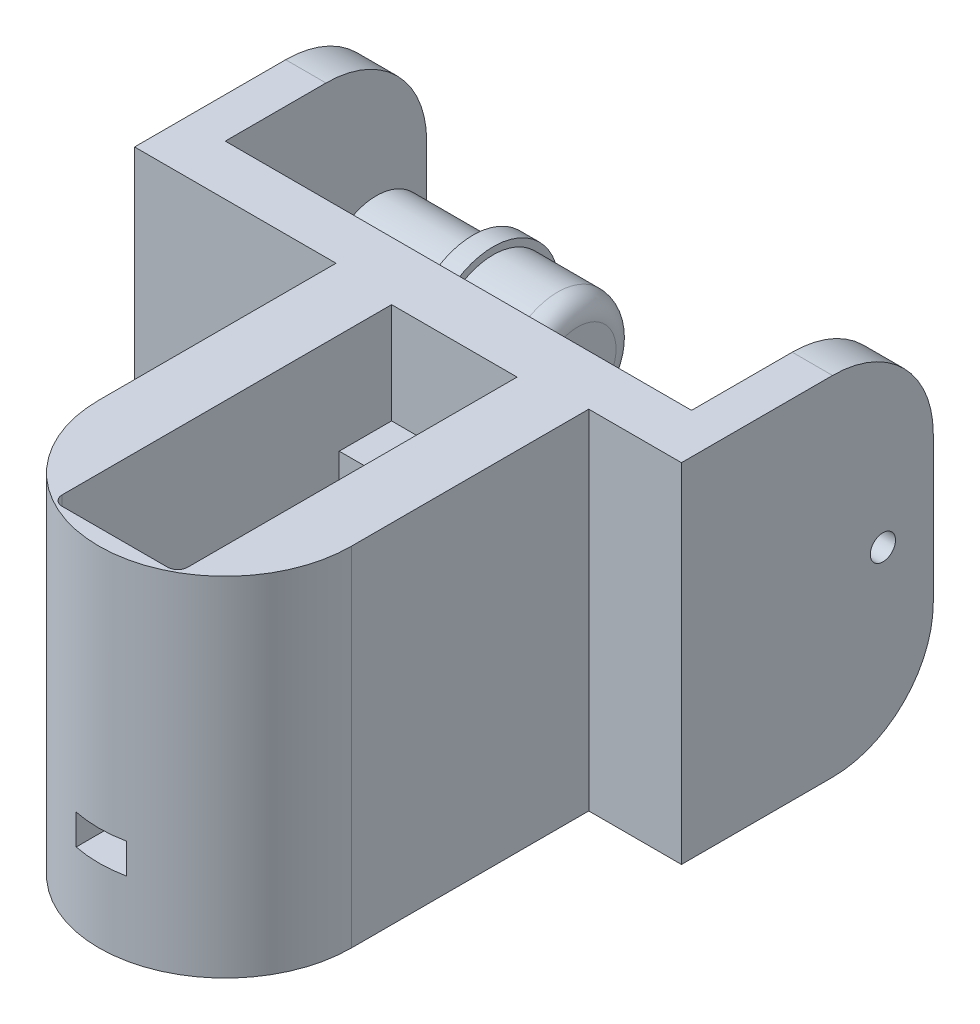
SolidWorks part; units mm, degrees
ref_plane "Front Plane" through (0, 0, 0) normal (0, 0, 1) x (1, 0, 0)
ref_plane "Top Plane" through (0, 0, 0) normal (0, 1, 0) x (1, 0, 0)
ref_plane "Right Plane" through (0, 0, 0) normal (1, 0, 0) x (0, 0, -1)
sketch "Sketch4" plane through (0, 0, 0) normal (0, 0, 1) x (1, 0, 0)
  line L1 (-6.23, -9.975) -> (6.23, -9.975)
  line L2 (-6.23, -9.975) -> (-6.23, 7.275)
  line L3 (-6.23, 7.275) -> (6.23, 7.275)
  line L4 (6.23, -9.975) -> (6.23, 7.275)
  point P4 (0, 7.275)
  dimension "D1" = 12.46
  dimension "D2" = 17.25
  dimension "D3" = 9.975
extrude "Boss-Extrude3" add sketch "Sketch4" along normal blind 6
sketch "Sketch8" plane through (0, -9.975, 0) normal (0, -1, 0) x (-1, 0, 0)
  circle A0 centre (0, -23.55) radius 12.5468
  circle A1 centre (0, -23.55) radius 11.15
  dimension "D1" = 22.3
  dimension "D2" = 23.55
extrude "Boss-Extrude6" add sketch "Sketch8" along normal blind 7.3 and the other way up to surface (17.25 mm away) other way up to face at (0, 7.275, 3)
sketch "Sketch5" plane through (0, 7.275, 0) normal (0, 1, 0) x (1, 0, 0)
  line L8 (12.5468, -23.55) -> (12.5468, 0)
  line L9 (12.5468, 0) -> (6.23, 0)
  line L10 (-12.5468, -23.55) -> (-12.5468, 0)
  line L11 (-12.5468, 0) -> (-6.23, 0)
  line L12 (-6.23, 0) -> (-6.23, -29.7)
  line L14 (6.23, -29.7) -> (6.23, 0)
  line L15 (-6.23, -29.7) -> (6.23, -29.7)
  line L16 (6.23, -6) -> (-6.23, -6) construction
  circle A0 centre (0, -23.55) radius 12.5468 construction
  arc A1 (-12.5468, -23.55) -> (12.5468, -23.55) centre (0, -23.55) ccw
  dimension "D1" = 23.7
  dimension "D2" = 23.55
extrude "Boss-Extrude4" add sketch "Sketch5" against normal up to surface (17.25 mm away) up to face at (0, -9.975, 3)
sketch "Sketch6" plane through (0, 7.275, 0) normal (0, 1, 0) x (1, 0, 0)
  line L0 (6.23, -6) -> (-6.23, -6) construction
  line L3 (6.23, -29.7) -> (-6.23, -29.7) construction
  circle A0 centre (0, -3.6) radius 0.5
  circle A1 centre (0, -32.1) radius 0.5
  dimension "D1" = 1
  dimension "D3" = 1
  dimension "D2" = 2.4
  dimension "D4" = 2.4
extrude "Cut-Extrude1" cut sketch "Sketch6" against normal blind 15
chamfer "Chamfer1" distance 0.5 angle 60 2 edges at (0, 7.275, 4.1) (0, 7.275, 32.6) first distance on face at (0, 7.275, 4.1)
sketch "Sketch10" plane through (0, 7.275, 0) normal (0, 1, 0) x (1, 0, 0)
  line L1 (-6.23, -6) -> (6.23, -6)
  line L2 (-6.23, -6) -> (-6.23, -29.7)
  line L3 (-6.23, -29.7) -> (6.23, -29.7)
  line L4 (6.23, -6) -> (6.23, -29.7)
extrude "Cut-Extrude3" cut sketch "Sketch10" against normal up to surface (17.25 mm away) up to face at (0, -9.975, 27.1007)
ref_plane "Plane1" through (0, 0, 36.0968) normal (0, 0, 1) x (1, 0, 0)
sketch "Sketch11" plane through (0, 0, 36.0968) normal (0, 0, 1) x (1, 0, 0)
  line L0 (-11.15, -9.975) -> (11.15, -9.975) construction
  line L1 (-2.5, -6.975) -> (2.5, -6.975)
  line L2 (-2.5, -6.975) -> (-2.5, -9.975)
  line L3 (-2.5, -9.975) -> (2.5, -9.975)
  line L4 (2.5, -6.975) -> (2.5, -9.975)
  point P4 (0, -6.975)
  dimension "D1" = 0
  dimension "D2" = 5
  dimension "D3" = 3
extrude "Cut-Extrude4" cut sketch "Sketch11" against normal up to next
sketch "Sketch13" plane through (0, -17.275, 0) normal (0, -1, 0) x (1, 0, 0)
  line L0 (-12.5468, 23.55) -> (-12.5468, 0)
  line L1 (-12.5468, 0) -> (12.5468, 0)
  line L2 (12.5468, 0) -> (12.5468, 23.55)
  arc A0 (-12.5468, 23.55) -> (12.5468, 23.55) centre (0, 23.55) ccw
  point P3 (0, 0)
extrude "Boss-Extrude7" add sketch "Sketch13" against normal up to surface (7.3 mm away) up to face at (-6.0145, -9.975, 27.3356)
sketch "Sketch15" plane through (0, 7.275, 0) normal (0, 1, 0) x (1, 0, 0)
  line L0 (-12.5468, 0) -> (12.5468, 0)
  line L1 (12.5468, 0) -> (12.5468, -23.55)
  line L2 (-12.5468, 0) -> (-12.5468, -23.55)
  line L3 (6.23, -6) -> (6.23, -29.7) construction
  line L4 (-6.23, -0.8) -> (6.23, -0.8)
  line L5 (-6.23, -0.8) -> (-6.23, -33.5)
  line L6 (-5.23, -34.5) -> (5.23, -34.5)
  line L7 (6.23, -0.8) -> (6.23, -33.5)
  arc A0 (-12.5468, -23.55) -> (12.5468, -23.55) centre (0, -23.55) ccw
  circle A1 centre (0, -3.6) radius 0.5 construction
  arc A2 (5.23, -34.5) -> (6.23, -33.5) centre (5.23, -33.5) ccw
  arc A3 (-6.23, -33.5) -> (-5.23, -34.5) centre (-5.23, -33.5) ccw
  point P15 (0, -0.8)
  dimension "D1" = 0.8
  dimension "D3" = 1
  dimension "D2" = 2.8
  dimension "D4" = 0
  dimension "D5" = 34.5
extrude "Boss-Extrude9" add sketch "Sketch15" along normal blind 10
sketch "Sketch20" plane through (0, -17.275, 0) normal (0, -1, 0) x (1, 0, 0)
  circle A0 centre (0, 23.55) radius 7.15
  circle A1 centre (0, 23.55) radius 11.15
  circle A2 centre (0, 23.55) radius 11.15 construction
  dimension "D1" = 14.3
extrude "Boss-Extrude11" add sketch "Sketch20" against normal up to surface (7.3 mm away) up to face at (-6.0145, -9.975, 27.3356)
sketch "Sketch21" plane through (0, -17.275, 0) normal (0, -1, 0) x (1, 0, 0)
  circle A0 centre (0, 23.55) radius 7.15
  circle A1 centre (0, 23.55) radius 10.15
  circle A2 centre (0, 23.55) radius 7.15 construction
  dimension "D1" = 20.3
extrude "Cut-Extrude7" cut sketch "Sketch21" against normal blind 1.3
sketch "Sketch17" plane through (0, 17.275, 0) normal (0, 1, 0) x (1, 0, 0)
  line L0 (21.75, 25) -> (21.75, 0)
  line L1 (21.75, 0) -> (-32.5468, 0)
  line L2 (-32.5468, 0) -> (-32.5468, 25)
  line L3 (-32.5468, 25) -> (-28.5468, 25)
  line L4 (-28.5468, 25) -> (-28.5468, 5)
  line L5 (-28.5468, 5) -> (17.75, 5)
  line L6 (17.75, 5) -> (17.75, 25)
  line L7 (17.75, 25) -> (21.75, 25)
  line L8 (-12.5468, -23.55) -> (-12.5468, 0) construction
  line L9 (12.5468, 0) -> (12.5468, -23.55) construction
  dimension "D1" = 4
  dimension "D2" = 5.2032
  dimension "D3" = 4
  dimension "D4" = 25
  dimension "D5" = 5
  dimension "D6" = 20
extrude "Boss-Extrude10" add sketch "Sketch17" against normal up to surface (34.55 mm away) up to face at (0, -17.275, 13.4)
sketch "Sketch18" plane through (17.75, 0, 0) normal (-1, 0, 0) x (0, 0, 1)
  line L0 (-25, -17.275) -> (-25, 17.275) construction
  line L1 (-25, 6.2191) -> (-5, 6.2191)
  line L2 (-25, 6.2191) -> (-25, -6.2191)
  line L3 (-25, -6.2191) -> (-5, -6.2191)
  line L4 (-5, 6.2191) -> (-5, -6.2191)
  line L5 (-5, -17.275) -> (-5, 17.275) construction
  point P6 (-25, 0)
  point P7 (-25, 0)
  dimension "D1" = 0
extrude "Cut-Extrude5" cut sketch "Sketch18" against normal blind 2
sketch "Sketch19" plane through (19.75, 0, 0) normal (-1, 0, 0) x (0, 0, 1)
  line L0 (-25, -17.275) -> (-25, 17.275) construction
  circle A0 centre (-20, 0) radius 1.25
  dimension "D1" = 2.5
  dimension "D2" = 5
extrude "Cut-Extrude6" cut sketch "Sketch19" against normal through all both and the other way through all
fillet "Fillet1" radius 10 4 edges at (19.75, -17.275, -25) (19.75, 17.275, -25) (-30.5468, 17.275, -25) (-30.5468, -17.275, -25)
ref_plane "Plane2" through (0, 0, 0) normal (1, 0, 0) x (0, 0, -1)
ref_plane "Plane3" through (0, 0, 0) normal (0, -1, 0) x (-1, 0, 0)
sketch "Sketch22" plane through (-28.5468, 0, 0) normal (1, 0, 0) x (0, 0, -1)
  circle A0 centre (20, 0) radius 5.8
  dimension "D1" = 11.6
extrude "Boss-Extrude12" add sketch "Sketch22" along normal blind 20
fillet "Fillet2" radius 2 1 edges at (-8.5468, 0, -25.8)
sketch "Sketch23" plane through (-28.5468, 0, 0) normal (1, 0, 0) x (0, 0, -1)
  circle A0 centre (20, 0) radius 5.08
  circle A1 centre (20, 0) radius 5.9309
  dimension "D1" = 10.16
extrude "Cut-Extrude8" cut sketch "Sketch23" along normal blind 11.6
sketch "Sketch24" plane through (-16.9468, 0, 0) normal (-1, 0, 0) x (0, 0, 1)
  circle A0 centre (-20, 0) radius 6.5
extrude "Boss-Extrude13" add sketch "Sketch24" along normal blind 2
sketch "Sketch25" plane through (-32.5468, 0, 0) normal (-1, 0, 0) x (0, 0, 1)
  circle A0 centre (-20, 0) radius 1.25
extrude "Boss-Extrude14" add sketch "Sketch25" against normal blind 2
sketch "Sketch26" plane through (-28.5468, 0, 0) normal (1, 0, 0) x (0, 0, -1)
  line L0 (5, -17.275) -> (5, 17.275) construction
  line L1 (5, -9.775) -> (10, -9.775)
  line L2 (5, -9.775) -> (5, -6.775)
  line L3 (5, -6.775) -> (10, -6.775)
  line L4 (10, -9.775) -> (10, -6.775)
  line L5 (0, -17.275) -> (15, -17.275) construction
  line L6 (5, -5.259) -> (10, -5.259)
  line L7 (5, -5.259) -> (5, -2.259)
  line L8 (5, -2.259) -> (10, -2.259)
  line L9 (10, -5.259) -> (10, -2.259)
  dimension "D1" = 1.516
  dimension "D2" = 3
  dimension "D3" = 3
  dimension "D4" = 0
  dimension "D5" = 5
  dimension "D6" = 7.5
extrude "Boss-Extrude15" add sketch "Sketch26" along normal blind 5
